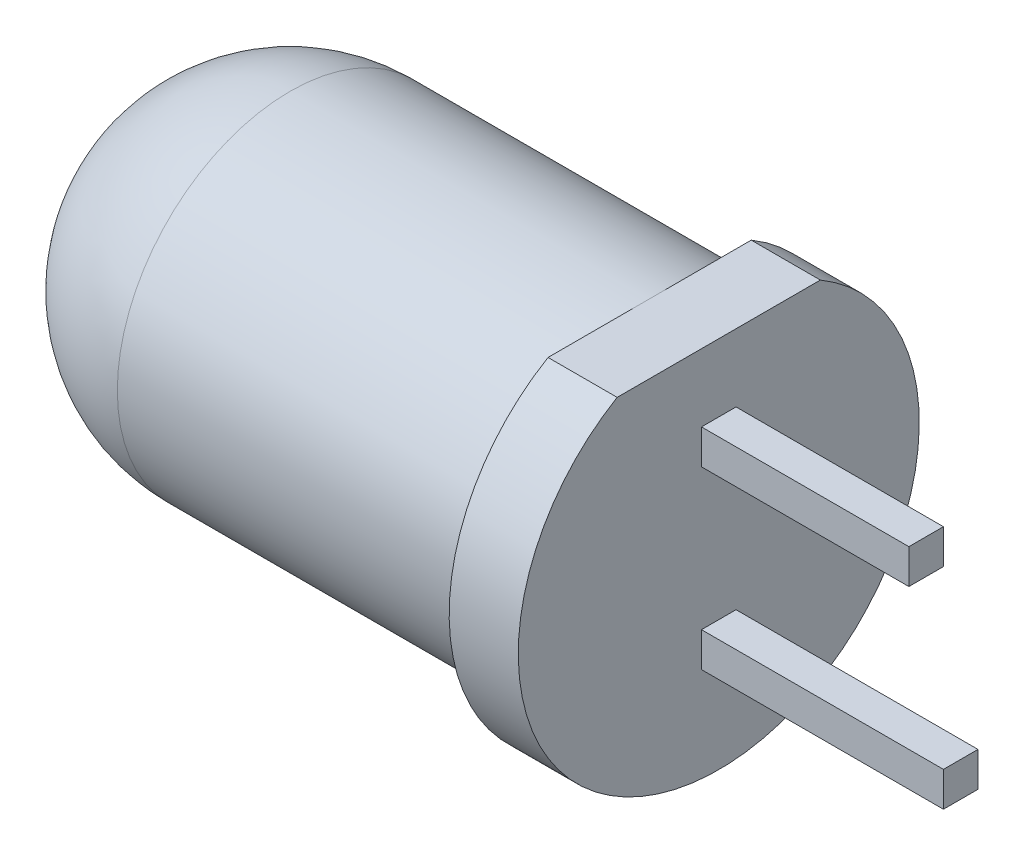
SolidWorks part; units mm, degrees
ref_plane "前视基准面" through (0, 0, 0) normal (0, 0, 1) x (1, 0, 0)
ref_plane "上视基准面" through (0, 0, 0) normal (0, 1, 0) x (1, 0, 0)
ref_plane "右视基准面" through (0, 0, 0) normal (1, 0, 0) x (0, 0, -1)
sketch "草图1" plane through (0, 0, 0) normal (0, 0, 1) x (1, 0, 0)
  line L0 (-3.1047, 0) -> (7.8623, 0) construction
  line L1 (0, 2.5) -> (5.2, 2.5)
  line L2 (-2.5, 0) -> (6.2, 0)
  line L3 (5.2, 2.5) -> (5.2, 2.9)
  line L4 (6.2, 2.5) -> (6.2, 0)
  line L5 (5.2, 2.9) -> (6.2, 2.9)
  line L6 (6.2, 2.9) -> (6.2, 2.5)
  arc A0 (0, 2.5) -> (-2.5, 0) centre (0, 0) ccw
  dimension "D1" = 5
  dimension "D2" = 8.7
  dimension "D3" = 1
  dimension "D4" = 0.4
revolve "旋转1" add sketch "草图1" angle 360 about L0
sketch "草图2" plane through (6.2, 0, 0) normal (1, 0, 0) x (0, 0, -1)
  line L0 (-4.1439, 0) -> (4.4026, 0) construction
  line L1 (0, 3.3981) -> (0, -3.7056) construction
  line L2 (-0.25, -1.52) -> (-0.25, -1.02)
  line L3 (-0.25, 1.52) -> (0.25, 1.52)
  line L4 (-0.25, 1.52) -> (-0.25, 1.02)
  line L5 (-0.25, 1.02) -> (0.25, 1.02)
  line L6 (0.25, 1.52) -> (0.25, 1.02)
  line L7 (-0.25, -1.52) -> (0.25, -1.52)
  line L8 (0.25, -1.52) -> (0.25, -1.02)
  line L9 (-0.25, -1.02) -> (0.25, -1.02)
  dimension "D1" = 0.5
  dimension "D2" = 0.5
  dimension "D3" = 2.54
sketch "草图4" plane through (6.2, 0, 0) normal (1, 0, 0) x (0, 0, -1)
  line L0 (-1.4697, 2.5) -> (1.4697, 2.5)
  line L1 (-4.1439, 0) -> (4.4026, 0) construction
  circle A0 centre (0, 0) radius 2.9 construction
  arc A1 (1.4697, 2.5) -> (-1.4697, 2.5) centre (0, 0) ccw
  dimension "D1" = 2.5
extrude "切除-拉伸1" cut sketch "草图4" against normal up to next
extrude "凸台-拉伸1" add sketch "草图2" along normal blind 3.5 contours L9 L2 L7 L8 region at (6.2, -1.27, 0)
extrude "凸台-拉伸2" add sketch "草图2<3>" along normal blind 3 contours L6 L3 L4 L5 region at (6.2, 1.27, 0)
sketch "草图2<3>" plane through (6.2, 0, 0) normal (1, 0, 0) x (0, 0, -1) same geometry as "草图2"
